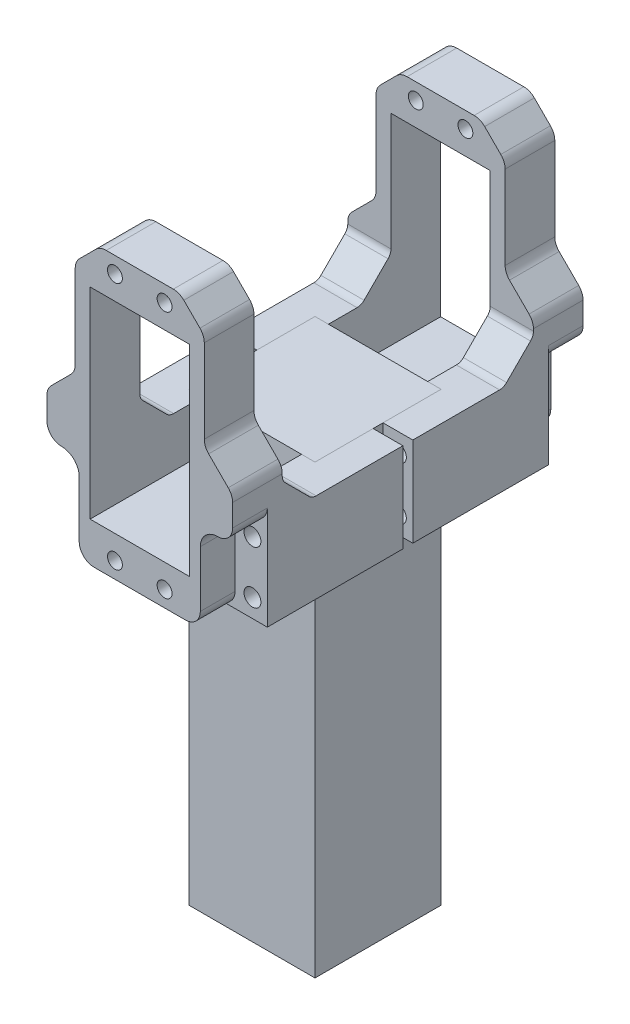
SolidWorks part; units mm, degrees
ref_plane "Front Plane" through (0, 0, 0) normal (0, 0, 1) x (1, 0, 0)
ref_plane "Top Plane" through (0, 0, 0) normal (0, 1, 0) x (1, 0, 0)
ref_plane "Right Plane" through (0, 0, 0) normal (1, 0, 0) x (0, 0, -1)
sketch "Sketch1" plane through (0, 0, 0) normal (0, 1, 0) x (1, 0, 0)
  line L1 (-12.7, 12.7) -> (12.7, 12.7)
  line L2 (-12.7, 12.7) -> (-12.7, -12.7)
  line L3 (-12.7, -12.7) -> (12.7, -12.7)
  line L4 (12.7, 12.7) -> (12.7, -12.7)
  line L5 (-12.7, 12.7) -> (12.7, -12.7) construction
  line L6 (-12.7, -12.7) -> (12.7, 12.7) construction
  point P0 (0, 0)
  dimension "D1" = 25.4
extrude "Boss-Extrude1" add sketch "Sketch1" against normal blind 90
sketch "Sketch2" plane through (0, 0, 0) normal (0, 0, 1) x (1, 0, 0)
  line L0 (0, 10.25) -> (0, 20.25) construction
  line L1 (-10, 30.5) -> (10, 30.5)
  line L2 (-10, 30.5) -> (-10, -10)
  line L3 (-10, -10) -> (10, -10)
  line L4 (10, 30.5) -> (10, -10)
  line L5 (-10, 30.5) -> (10, -10) construction
  line L6 (-10, -10) -> (10, 30.5) construction
  line L7 (-18.7, -18) -> (18.7, -18)
  line L8 (-18.7, -18) -> (-18.7, 38.5)
  line L9 (-18.7, 38.5) -> (18.7, 38.5)
  line L10 (18.7, 38.5) -> (18.7, -18)
  line L11 (12.7, -90) -> (12.7, 0) construction
  line L12 (-12.7, 0) -> (12.7, 0) construction
  point P0 (0, 10.25)
  dimension "D1" = 40.5
  dimension "D2" = 10
  dimension "D3" = 20
  dimension "D4" = 8
  dimension "D5" = 8
  dimension "D6" = 6
  dimension "D7" = 18
extrude "Boss-Extrude2" add sketch "Sketch2" along normal blind 10 from offset 25.3 separate body
sketch "Sketch3" plane through (0, 0, 25.3) normal (0, 0, -1) x (-1, 0, 0)
  line L0 (-12.7, -90) -> (-12.7, 0) construction
  line L1 (-18.7, -18) -> (-12.7, -18)
  line L2 (-18.7, -18) -> (-18.7, 0)
  line L3 (-18.7, 0) -> (-12.7, 0)
  line L4 (-12.7, -18) -> (-12.7, 0)
  line L5 (-18.7, 38.5) -> (-18.7, -18) construction
  line L6 (0, 0) -> (0, 9.17) construction
  line L7 (18.7, 0) -> (12.7, 0)
  line L8 (12.7, -18) -> (12.7, 0)
  line L9 (18.7, -18) -> (12.7, -18)
  line L10 (18.7, -18) -> (18.7, 0)
  line L11 (12.7, 0) -> (18.7, -18) construction
  line L12 (15.7, -14.3) -> (15.7, -3.7) construction
  circle A0 centre (15.7, -3.7) radius 1.7
  circle A1 centre (15.7, -14.3) radius 1.7
  circle A2 centre (-15.7, -14.3) radius 1.7
  circle A3 centre (-15.7, -3.7) radius 1.7
  point P20 (15.7, -9)
  dimension "D1" = 3.4
  dimension "D2" = 2
extrude "Boss-Extrude3" add sketch "Sketch3" along normal offset from surface (24.3 mm away) 1 up to plane "Front Plane"
sketch "Sketch6" plane through (0, 0, 25.3) normal (0, 0, -1) x (-1, 0, 0)
  line L0 (-12.7, -18) -> (-12.7, 0)
  line L1 (-12.7, 0) -> (-10, 0)
  line L2 (-10, 30.5) -> (-10, -10) construction
  line L3 (-12.7, 0) -> (12.7, 0) construction
  line L4 (-10, 0) -> (-10, -10)
  line L5 (-10, -10) -> (10, -10)
  line L6 (10, -10) -> (10, 0)
  line L7 (10, 30.5) -> (10, -10) construction
  line L8 (10, 0) -> (12.7, 0)
  line L9 (12.7, 0) -> (12.7, -18)
  line L10 (12.7, -18) -> (-12.7, -18)
extrude "Boss-Extrude4" add sketch "Sketch6" along normal up to surface (12.6 mm away) up to face at (0, -45, 12.7)
extrude "Cut-Extrude1" cut sketch "Sketch3<2>" against normal through all contours A3 | A2 | A0 | A1
sketch "Sketch3<2>" plane through (0, 0, 25.3) normal (0, 0, -1) x (-1, 0, 0) same geometry as "Sketch3"
sketch "Sketch7" plane through (0, 0, 35.3) normal (0, 0, 1) x (1, 0, 0)
  line L0 (-18.7, 8.5) -> (-13, 14.2)
  line L1 (-18.7, 38.5) -> (-18.7, -18) construction
  line L2 (-13, 14.2) -> (-13, 38.5)
  line L3 (18.7, 38.5) -> (-18.7, 38.5) construction
  line L4 (-10, 30.5) -> (-10, -10) construction
  line L5 (-13, 38.5) -> (-18.7, 38.5)
  line L6 (-18.7, 38.5) -> (-18.7, 8.5)
  line L7 (0, 0) -> (0, 6.862) construction
  line L8 (-12.7, 0) -> (12.7, 0) construction
  line L9 (13, 38.5) -> (18.7, 38.5)
  line L10 (13, 14.2) -> (13, 38.5)
  line L11 (18.7, 8.5) -> (13, 14.2)
  line L12 (18.7, 38.5) -> (18.7, 8.5)
  dimension "D1" = 3
  dimension "D2" = 45
  dimension "D3" = 30
extrude "Cut-Extrude2" cut sketch "Sketch7" against normal through all
chamfer "Chamfer3" distance 5 angle 45 2 edges at (13, 38.5, 30.3) (-13, 38.5, 30.3)
fillet "Fillet4" radius 3 4 edges at (-13, 33.5, 30.3) (-8, 38.5, 30.3) (13, 33.5, 30.3) (8, 38.5, 30.3)
ref_axis "Axis1" through (0, 20.25, 0) along (0, 0, -1)
sketch "Sketch5" plane through (0, 0, 0) normal (0, 0, 1) x (1, 0, 0)
  circle A0 centre (0, 20.25) radius 19.75
  dimension "D1" = 39.5
sketch "Sketch8" plane through (0, 0, 35.3) normal (0, 0, 1) x (1, 0, 0)
  line L0 (15.7, -0.2) -> (18.7, -0.2)
  line L1 (18.7, -18) -> (18.7, 8.5) construction
  line L2 (12.2, -3.7) -> (12.2, -18)
  line L3 (-18.7, -18) -> (18.7, -18) construction
  line L4 (12.2, -18) -> (31.6073, -25.9921)
  line L5 (31.6073, -25.9921) -> (18.7, -0.2)
  line L6 (0, 0) -> (0, 6.1981) construction
  line L7 (-12.2, -3.7) -> (-12.2, -18)
  line L8 (-12.2, -18) -> (-31.6073, -25.9921)
  line L9 (-31.6073, -25.9921) -> (-18.7, -0.2)
  line L10 (-15.7, -0.2) -> (-18.7, -0.2)
  arc A0 (15.7, -0.2) -> (12.2, -3.7) centre (15.7, -3.7) ccw
  arc A1 (-15.7, -0.2) -> (-12.2, -3.7) centre (-15.7, -3.7) cw
  dimension "D1" = 7
extrude "Cut-Extrude3" cut sketch "Sketch8" against normal blind 7
sketch "Sketch10" plane through (0, 0, 35.3) normal (0, 0, 1) x (1, 0, 0)
  line L0 (0, 35.25) -> (0, -14.75) construction
  line L1 (-10, 30.5) -> (10, -10) construction
  line L2 (-5, 35.25) -> (5, 35.25) construction
  line L3 (-5, -14.75) -> (5, -14.75) construction
  circle A0 centre (-5, 35.25) radius 1.5
  circle A1 centre (5, 35.25) radius 1.5
  circle A2 centre (-5, -14.75) radius 1.5
  circle A3 centre (5, -14.75) radius 1.5
  point P7 (0, 10.25)
  dimension "D1" = 3
  dimension "D2" = 50
  dimension "D3" = 10
extrude "Cut-Extrude4" cut sketch "Sketch10" against normal blind 15
chamfer "Chamfer2" distance 6 angle 45 2 edges at (-14.35, 0, 25.3) (14.35, 0, 25.3)
fillet "Fillet2" radius 2 4 edges at (-14.35, 0, 19.3) (-14.35, 6, 25.3) (14.35, 6, 25.3) (14.35, 0, 19.3)
fillet "Fillet3" radius 3 8 edges at (-13, 14.2, 30.3) (-18.7, 8.5, 30.3) (-18.7, -0.2, 31.8) (-12.2, -18, 31.8) (12.2, -18, 31.8) (18.7, -0.2, 31.8) (18.7, 8.5, 30.3) (13, 14.2, 30.3)
mirror "Mirror1" about plane through (0, 0, 0) normal (0, 0, 1) of bodies 110 107
